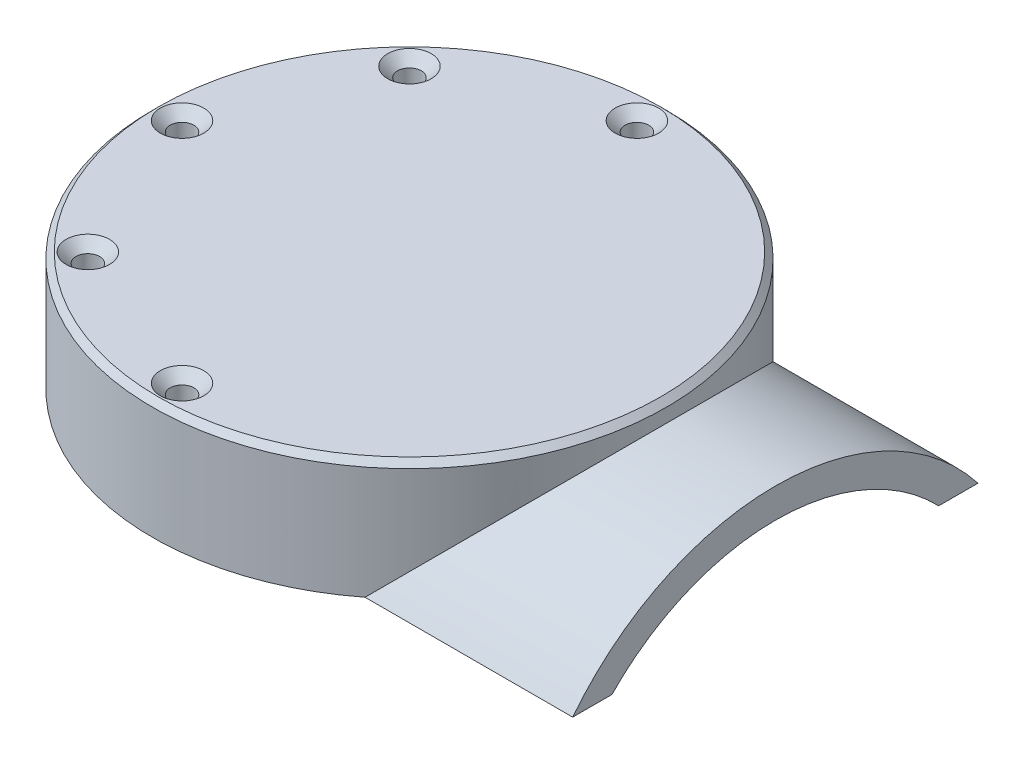
SolidWorks part; units mm, degrees
material "ПК/АБС"
ref_plane "Спереди" through (0, 0, 0) normal (0, 0, 1) x (1, 0, 0)
ref_plane "Сверху" through (0, 0, 0) normal (0, 1, 0) x (1, 0, 0)
ref_plane "Справа" through (0, 0, 0) normal (1, 0, 0) x (0, 0, -1)
sketch "Эскиз1" plane through (0, 0, 0) normal (0, 0, 1) x (1, 0, 0)
  line L0 (0, 0) -> (0, 41295.6463) construction
  line L1 (0, 0) -> (-26, 0)
  line L2 (-26, 0) -> (-26, 28)
  line L3 (-26, 28) -> (0, 28)
  line L4 (0, 28) -> (0, 0)
  line L5 (0, 0) -> (-50000, 0) construction
  dimension "D1" = 52
  dimension "D2" = 28
revolve "Повернуть1" add sketch "Эскиз1" angle 360 about L0
sketch "Эскиз2" plane through (0, 0, 0) normal (0, 0, 1) x (1, 0, 0)
  line L0 (0, 0) -> (50000, 0) construction
  line L1 (-26, 0) -> (26, 0) construction
  line L2 (0, 0) -> (0, 26)
  line L3 (0, 26) -> (37, 26)
  line L4 (37, 26) -> (37, 0)
  line L5 (37, 0) -> (0, 0)
  point P4 (0, 0)
  dimension "D1" = 52
  dimension "D2" = 37
revolve "Повернуть2" add sketch "Эскиз2" angle 360 about L0
chamfer "Фаска1" distance 0.6 angle 45 1 edges at (0, 28, -26)
sketch "Эскиз4" plane through (0, 0, 0) normal (0, 0, 1) x (1, 0, 0)
  line L0 (0, 0) -> (0, 50000) construction
  line L1 (0, 0) -> (-21, 0)
  line L2 (-21, 0) -> (-21, 26)
  line L3 (-21, 26) -> (0, 26)
  line L4 (0, 26) -> (0, 0)
  line L5 (37, 26) -> (26, 26) construction
  dimension "D1" = 42
revolve "Вырез-Повернуть1" cut sketch "Эскиз4" angle 360 about L0
sketch "Эскиз5" plane through (0, 0, 0) normal (0, 0, 1) x (1, 0, 0)
  line L0 (0, 0) -> (50000, 0) construction
  line L2 (0, 0) -> (0, 23)
  line L3 (0, 23) -> (37, 23)
  line L4 (37, -26) -> (37, 26) construction
  line L5 (37, 23) -> (37, 0)
  line L6 (37, 0) -> (0, 0)
  dimension "D1" = 46
revolve "Вырез-Повернуть2" cut sketch "Эскиз5" angle 360 about L0
sketch "Эскиз6" plane through (0, 0, 0) normal (0, 1, 0) x (1, 0, 0)
  line L0 (0, 26) -> (37, 26)
  line L1 (37, 26) -> (37, -26)
  line L2 (37, -26) -> (0, -26)
  line L3 (0, -26) -> (37, -26) construction
  circle A0 centre (0, 0) radius 26 construction
  arc A1 (0, -26) -> (0, 26) centre (0, 0) ccw construction
  arc A2 (0, -26) -> (0, 26) centre (0, 0) cw
  point P16 (0, 0)
  point P18 (0, -25)
extrude "Вырез-Вытянуть1" cut sketch "Эскиз6" against normal through all and the other way blind 16
hole_wizard "Зенковка для винта с потайной головкой M21" positions "Эскиз7" profile "Эскиз8" countersink size "M2" standard "HASCO Metric" end condition through all
sketch "Эскиз7" plane through (0, 28, 0) normal (0, 1, 0) x (1, 0, 0)
  line L0 (0, 0) -> (-25.4, 0) construction
  circle A0 centre (0, 0) radius 25.4 construction
  circle A1 centre (0, 0) radius 23 construction
  point P0 (-23, 0)
  point P14 (-23, 0)
  dimension "D1" = 46
sketch "Эскиз8" plane through (-23, 28, 0) normal (1, 0, 0) x (0, 0, 1)
  line L0 (0, 0) -> (0, 13.2612)
  line L1 (0, 13.2612) -> (1.2, 13.2612)
  line L2 (1.2, 13.2612) -> (1.2, 1)
  line L3 (1.2, 1) -> (2.2, 0)
  line L5 (2.2, 0) -> (0, 0)
  line L6 (-1.2, 1) -> (-2.2, 0) construction
  line L11 (0, -6.35) -> (0, 107.95) construction
  dimension "Диаметр сквозного отверстия" = 2.4
  dimension "Глубина сквозного отверстия" = 13.2612
  dimension "Диаметр передней зенковки" = 4.4
  dimension "Угол передней зенковки" = 90
pattern_circular "Круговой массив1" count 3 every 45 about axis through (0, 28, 0) along (0, 1, 0) of "Зенковка для винта с потайной головкой M21" other way count 3
